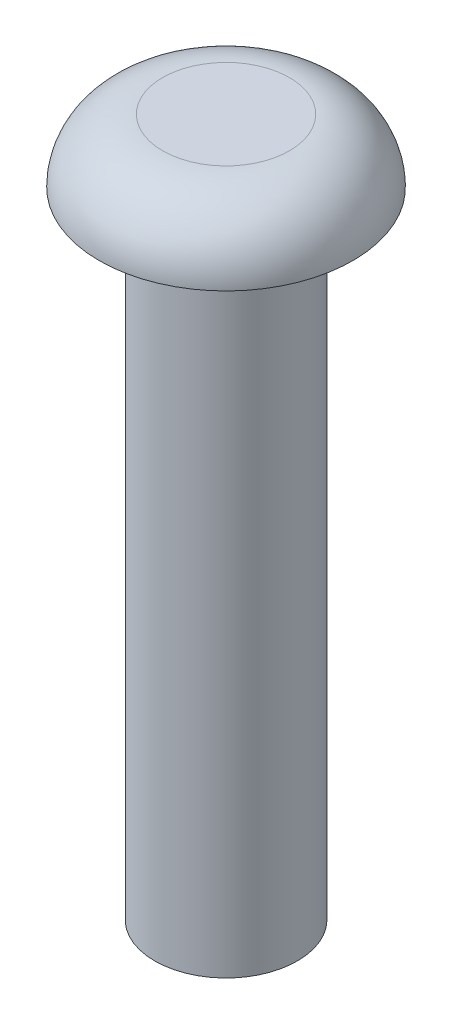
SolidWorks part; units mm, degrees
ref_plane "Front Plane" through (0, 0, 0) normal (0, 0, 1) x (1, 0, 0)
ref_plane "Top Plane" through (0, 0, 0) normal (0, 1, 0) x (1, 0, 0)
ref_plane "Right Plane" through (0, 0, 0) normal (1, 0, 0) x (0, 0, -1)
sketch "Sketch1" plane through (0, 0, 0) normal (0, 1, 0) x (1, 0, 0)
  circle A0 centre (0, 0) radius 2.25
  dimension "D1" = 4.5
extrude "Boss-Extrude1" add sketch "Sketch1" along normal blind 20
sketch "Sketch2" plane through (0, 20, 0) normal (0, 1, 0) x (1, 0, 0)
  circle A0 centre (0, 0) radius 4
  dimension "D1" = 8
extrude "Boss-Extrude2" add sketch "Sketch2" along normal blind 2
fillet "Fillet1" radius 2 1 edges at (0, 22, 4)
